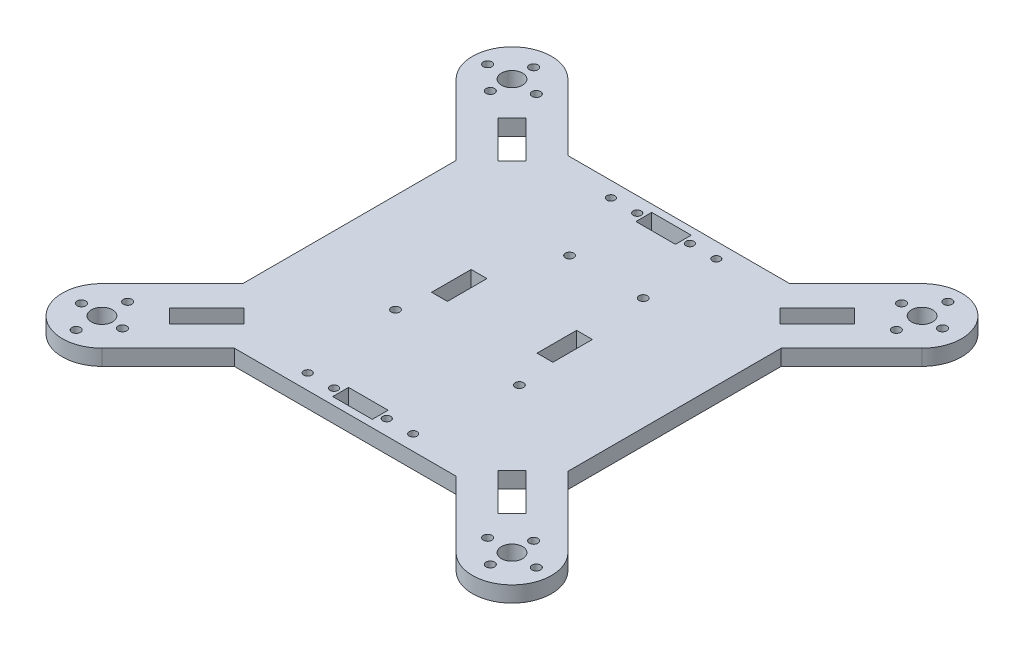
SolidWorks part; units mm, degrees
ref_plane "Front Plane" through (0, 0, 0) normal (0, 0, 1) x (1, 0, 0)
ref_plane "Top Plane" through (0, 0, 0) normal (0, 1, 0) x (1, 0, 0)
ref_plane "Right Plane" through (0, 0, 0) normal (1, 0, 0) x (0, 0, -1)
sketch "Sketch1" plane through (0, 0, 0) normal (0, 1, 0) x (1, 0, 0)
  line L0 (-67.1751, 88.3883) -> (88.3883, -67.1751)
  line L1 (-77.7817, 77.7817) -> (77.7817, 77.7817) construction
  line L2 (-77.7817, 77.7817) -> (-77.7817, -77.7817) construction
  line L3 (-77.7817, -77.7817) -> (77.7817, -77.7817) construction
  line L4 (77.7817, 77.7817) -> (77.7817, -77.7817) construction
  line L5 (-77.7817, 77.7817) -> (77.7817, -77.7817) construction
  line L6 (-77.7817, -77.7817) -> (77.7817, 77.7817) construction
  line L7 (67.1751, 88.3883) -> (-88.3883, -67.1751)
  line L8 (88.3883, 67.1751) -> (-67.1751, -88.3883)
  line L9 (-88.3883, 67.1751) -> (67.1751, -88.3883)
  line L10 (0, -1000) -> (0, 49000) construction
  line L11 (-1000, 0) -> (49000, 0) construction
  circle A0 centre (-77.7817, 77.7817) radius 15
  circle A1 centre (77.7817, 77.7817) radius 15
  circle A2 centre (-77.7817, -77.7817) radius 15
  circle A3 centre (77.7817, -77.7817) radius 15
  circle A4 centre (-77.7817, 77.7817) radius 4
  circle A5 centre (77.7817, 77.7817) radius 4
  circle A6 centre (77.7817, -77.7817) radius 4
  circle A7 centre (-77.7817, -77.7817) radius 4
  point P0 (0, 0)
  point P14 (10.6066, 10.6066)
  point P16 (10.6066, -10.6066)
  dimension "D4" = 8
  dimension "D1" = 220
  dimension "D2" = 30
  dimension "D3" = 30
extrude "Boss-Extrude1" add sketch "Sketch1" along normal blind 6 contours A0 A4 | A0 L9 L7 L0 | A2 A7 | L7 A2 L8 L9 | A3 L0 L8 L9 | L8 A1 L7 L0 | L7 L9 L8 L0 | A3 A6 | A1 A5 region at (-40.0766, 0, -40.0766) region at (-64.3155, 0, -83.3596) region at (40.0766, 0, -40.0766) region at (0, 0, 0) region at (40.0766, 0, 40.0766) region at (83.3596, 0, -91.248) region at (-40.0766, 0, 40.0766) region at (91.248, 0, 72.2039) region at (-72.2039, 0, 64.3155)
sketch "Sketch5" plane through (0, 6, 0) normal (0, 1, 0) x (1, 0, 0)
  line L0 (26.67, -35.3069) -> (-26.67, -35.3069)
  line L1 (26.67, -35.3069) -> (26.67, 30.7331)
  line L2 (21.59, 33.2731) -> (-11.176, 33.2731)
  line L3 (-26.67, -35.3069) -> (-26.67, 30.7331)
  line L4 (-26.67, 30.7331) -> (-13.716, 30.7331)
  line L5 (-13.716, 30.7331) -> (-11.176, 33.2731)
  line L6 (21.59, 33.2731) -> (24.13, 30.7331)
  line L7 (24.13, 30.7331) -> (26.67, 30.7331)
  line L8 (0, -1000) -> (0, 49000) construction
  line L10 (-1000, 0) -> (49000, 0) construction
  circle A0 centre (19.05, 30.7331) radius 1.5875
  circle A1 centre (-8.89, 30.7331) radius 1.5875
  circle A2 centre (24.13, -21.3369) radius 1.5875
  circle A3 centre (-24.13, -20.0669) radius 1.5875
  point P20 (0, -35.3069)
  line M10 (0, 21.2132) -> (-67.1751, 88.3883)
  line M12 (-88.3883, 67.1751) -> (-21.2132, 0)
  line M13 (-21.2132, 0) -> (-88.3883, -67.1751)
  line M15 (-67.1751, -88.3883) -> (0, -21.2132)
  line M16 (0, -21.2132) -> (67.1751, -88.3883)
  line M18 (88.3883, -67.1751) -> (21.2132, 0)
  line M19 (21.2132, 0) -> (88.3883, 67.1751)
  line M21 (67.1751, 88.3883) -> (0, 21.2132)
  dimension "D5" = 3.175
  dimension "D1" = 2.54
  dimension "D2" = 45
  dimension "D3" = 40.386
  dimension "D4" = 45
  dimension "D6" = 35.56
  dimension "D7" = 7.62
  dimension "D8" = 2.54
  dimension "D9" = 50.8
  dimension "D10" = 13.97
  dimension "D11" = 15.24
  dimension "D12" = 53.34
  dimension "D13" = 66.04
  dimension "D14" = 3.5921
  dimension "D15" = 2.54
  dimension "D16" = 2.54
  dimension "D17" = 2.54
  dimension "D18" = 32.766
  dimension "D19" = 66.04
  dimension "D20" = 12.954
extrude "Boss-Extrude2" add sketch "Sketch5" against normal blind 6 contours A1 M10 | A1 L5 L4 L3 L0 L1 L7 L6 L2 A3 A2 A0 M10 M12 M13 M15 M16 M18 M19 M21 | L3 M13 M12 | L1 M18 M19 | L0 M16 M15 | A1 L2 L5 M10 M21 region at (0.1063, 6, 1.0525) region at (0, 6, 30.609) region at (24.8511, 6, 0) region at (-24.8511, 6, 0) region at (0.3445, 6, -29.1791) region at (-8.5785, 6, -31.0446)
extrude "Cut-Extrude1" cut sketch "Sketch5<3>" against normal through all contours A1 | A0 | A2 | A3
sketch "Sketch5<3>" plane through (0, 6, 0) normal (0, 1, 0) x (1, 0, 0) same geometry as "Sketch5"
sketch "Sketch6" plane through (0, 6, 0) normal (0, 1, 0) x (1, 0, 0)
  line L0 (-1000, 0) -> (49000, 0) construction
  line L1 (0, -1000) -> (0, 49000) construction
  line L2 (0, 0) -> (-35355.3391, 35355.3391) construction
  line L3 (0, 0) -> (35355.3391, 35355.3391) construction
  line L4 (-77.5182, -68.2854) -> (-78.0453, -87.2781) construction
  line L5 (-69.7848, -78.0037) -> (-85.7787, -77.5598) construction
  circle A4 centre (-69.7848, -78.0037) radius 1.625
  circle A5 centre (-78.0453, -87.2781) radius 1.625
  circle A6 centre (-77.5182, -68.2854) radius 1.625
  circle A7 centre (-85.7787, -77.5598) radius 1.625
  circle A28 centre (-77.7817, -77.7817) radius 4 construction
  circle A29 centre (-77.7817, -77.7817) radius 4
  circle A30 centre (68.2854, -77.5182) radius 1.625
  circle A31 centre (87.2781, -78.0453) radius 1.625
  circle A32 centre (78.0037, -69.7848) radius 1.625
  circle A33 centre (77.5598, -85.7787) radius 1.625
  circle A38 centre (-87.2781, 78.0453) radius 1.625
  circle A39 centre (-77.5598, 85.7787) radius 1.625
  circle A40 centre (-78.0037, 69.7848) radius 1.625
  circle A41 centre (-68.2854, 77.5182) radius 1.625
  circle A42 centre (78.0453, 87.2781) radius 1.625
  circle A43 centre (77.5182, 68.2854) radius 1.625
  circle A44 centre (85.7787, 77.5598) radius 1.625
  circle A45 centre (69.7848, 78.0037) radius 1.625
  dimension "D1" = 18.9927
  dimension "D2" = 15.9938
  dimension "D3" = 9.7183
  dimension "D4" = 12.4197
  dimension "D5" = 12.4197
  dimension "D6" = 12.4197
extrude "Cut-Extrude2" cut sketch "Sketch6" against normal up to next (6 mm away)
sketch "Sketch7" plane through (0, 6, 0) normal (0, 1, 0) x (1, 0, 0)
  line L0 (88.3883, 67.1751) -> (26.67, 5.4568) construction
  line L1 (26.67, -5.4568) -> (26.67, 5.4568) construction
  line L2 (26.67, -5.4568) -> (88.3883, -67.1751) construction
  line L3 (-26.67, -5.4568) -> (-88.3883, -67.1751) construction
  line L4 (-88.3883, 67.1751) -> (-26.67, 5.4568) construction
  line L5 (-26.67, -5.4568) -> (-26.67, 5.4568) construction
  line L6 (88.3883, 67.1751) -> (26.67, 5.4568)
  line L7 (26.67, -5.4568) -> (26.67, 5.4568)
  line L8 (26.67, -5.4568) -> (88.3883, -67.1751)
  line L9 (-26.67, -5.4568) -> (-88.3883, -67.1751)
  line L10 (-88.3883, 67.1751) -> (-26.67, 5.4568)
  line L11 (-26.67, -5.4568) -> (-26.67, 5.4568)
  line L12 (-61.67, 40.4568) -> (-61.67, -40.4568)
  line L13 (0, -1000) -> (0, 49000) construction
  line L14 (61.67, 40.4568) -> (61.67, -40.4568)
  line L15 (-11.6179, 32.8311) -> (-11.176, 33.2731) construction
  line L16 (67.1751, 88.3883) -> (12.0599, 33.2731) construction
  line L17 (12.0599, 33.2731) -> (-11.176, 33.2731) construction
  line L18 (-67.1751, 88.3883) -> (-11.6179, 32.8311) construction
  line L19 (-11.6179, 32.8311) -> (-11.176, 33.2731)
  line L20 (67.1751, 88.3883) -> (12.0599, 33.2731)
  line L21 (12.0599, 33.2731) -> (-11.176, 33.2731)
  line L22 (-67.1751, 88.3883) -> (-11.6179, 32.8311)
  line L23 (14.0937, -35.3069) -> (67.1751, -88.3883) construction
  line L24 (14.0937, -35.3069) -> (-14.0937, -35.3069) construction
  line L25 (-14.0937, -35.3069) -> (-67.1751, -88.3883) construction
  line L26 (14.0937, -35.3069) -> (67.1751, -88.3883)
  line L27 (14.0937, -35.3069) -> (-14.0937, -35.3069)
  line L28 (-14.0937, -35.3069) -> (-67.1751, -88.3883)
  line L29 (-1000, 0) -> (49000, 0) construction
  line L30 (-42.0599, 63.2731) -> (42.0599, 63.2731)
  line L31 (-42.0599, -63.2731) -> (42.0599, -63.2731)
  line M25 (-14.0937, -35.3069) -> (14.0937, -35.3069)
  line M26 (14.0937, -35.3069) -> (67.1751, -88.3883)
  line M29 (26.67, -5.4568) -> (26.67, 5.4568)
  line M30 (26.67, 5.4568) -> (88.3883, 67.1751)
  line M33 (12.0599, 33.2731) -> (-11.176, 33.2731)
  line M34 (-11.176, 33.2731) -> (-11.6179, 32.8311)
  line M35 (-11.6179, 32.8311) -> (-67.1751, 88.3883)
  line M38 (-26.67, 5.4568) -> (-26.67, -5.4568)
  line M39 (-26.67, -5.4568) -> (-88.3883, -67.1751)
  dimension "D1" = 35
  dimension "D2" = 30
extrude "Boss-Extrude3" add sketch "Sketch7" against normal blind 6 contours L14 L8 M30 M29 | L10 L12 M39 M38 | L28 L31 M26 M25 | L30 L20 M35 M34 M33 region at (48.6168, 6, 0) region at (-48.6168, 6, 0) region at (-0.0014, 6, -51.0425) region at (0, 6, 51.6113)
sketch "Sketch8" plane through (0, 6, 0) normal (0, 1, 0) x (1, 0, 0)
  line L0 (0, -1000) -> (0, 49000) construction
  line L1 (-1000, 0) -> (49000, 0) construction
  line L2 (-20, 57.5) -> (20, 57.5) construction
  line L3 (-20, -57.5) -> (-20, 57.5) construction
  line L4 (-20, -57.5) -> (20, -57.5) construction
  line L5 (20, 57.5) -> (20, -57.5) construction
  line L6 (-7.5, -54.5) -> (7.5, -60.5) construction
  line L7 (-7.5, 60.5) -> (7.5, 60.5)
  line L8 (-7.5, 60.5) -> (-7.5, 54.5)
  line L9 (-7.5, 54.5) -> (7.5, 54.5)
  line L10 (7.5, 60.5) -> (7.5, 54.5)
  line L11 (-7.5, 60.5) -> (7.5, 54.5) construction
  line L12 (-7.5, 54.5) -> (7.5, 60.5) construction
  line L13 (-7.5, -60.5) -> (7.5, -54.5) construction
  line L14 (7.5, -60.5) -> (7.5, -54.5)
  line L15 (-7.5, -54.5) -> (7.5, -54.5)
  line L16 (-7.5, -60.5) -> (-7.5, -54.5)
  line L17 (-7.5, -60.5) -> (7.5, -60.5)
  line L18 (23, -7.5) -> (17, 7.5) construction
  line L19 (-23, 7.5) -> (-17, 7.5)
  line L20 (-23, 7.5) -> (-23, -7.5)
  line L21 (-23, -7.5) -> (-17, -7.5)
  line L22 (-17, 7.5) -> (-17, -7.5)
  line L23 (-23, 7.5) -> (-17, -7.5) construction
  line L24 (-23, -7.5) -> (-17, 7.5) construction
  line L25 (23, 7.5) -> (17, -7.5) construction
  line L26 (17, 7.5) -> (17, -7.5)
  line L27 (23, -7.5) -> (17, -7.5)
  line L28 (23, 7.5) -> (23, -7.5)
  line L29 (23, 7.5) -> (17, 7.5)
  circle A0 centre (-20, 57.5) radius 1.5
  circle A1 centre (20, 57.5) radius 1.5
  circle A2 centre (20, -57.5) radius 1.5
  circle A3 centre (-20, -57.5) radius 1.5
  circle A4 centre (-10, 57.5) radius 1.5
  circle A5 centre (10, 57.5) radius 1.5
  circle A6 centre (-10, -57.5) radius 1.5
  circle A7 centre (10, -57.5) radius 1.5
  point P15 (0, 57.5)
  point P32 (0, -57.5)
  point P33 (-20, 0)
  point P41 (20, 0)
  dimension "D3" = 3
  dimension "D4" = 3
  dimension "D5" = 3
  dimension "D6" = 3
  dimension "D8" = 3
  dimension "D1" = 40
  dimension "D2" = 115
  dimension "D7" = 10
  dimension "D9" = 6
  dimension "D10" = 15
  dimension "D11" = 6
  dimension "D12" = 15
extrude "Cut-Extrude7" cut sketch "Sketch8" along normal blind 6 and the other way through all
sketch "Sketch9" plane through (0, 6, 0) normal (0, 1, 0) x (1, 0, 0)
  line L0 (-1000, 0) -> (49000, 0) construction
  line L1 (0, -1000) -> (0, 49000) construction
  line L2 (0, 0) -> (-35355.3391, 35355.3391) construction
  line L3 (-67.6003, 62.297) -> (-62.297, 67.6003)
  line L4 (-67.6003, 62.297) -> (-53.4581, 48.1548)
  line L5 (-53.4581, 48.1548) -> (-48.1548, 53.4581)
  line L6 (-62.297, 67.6003) -> (-48.1548, 53.4581)
  line L7 (-67.6003, 62.297) -> (-48.1548, 53.4581) construction
  line L8 (-53.4581, 48.1548) -> (-62.297, 67.6003) construction
  line L9 (0, 0) -> (35355.3391, 35355.3391) construction
  line L10 (-88.3883, 67.1751) -> (-61.67, 40.4568) construction
  line L11 (53.4581, 48.1548) -> (62.297, 67.6003) construction
  line L12 (67.6003, 62.297) -> (48.1548, 53.4581) construction
  line L13 (62.297, 67.6003) -> (48.1548, 53.4581)
  line L14 (53.4581, 48.1548) -> (48.1548, 53.4581)
  line L15 (67.6003, 62.297) -> (53.4581, 48.1548)
  line L16 (67.6003, 62.297) -> (62.297, 67.6003)
  line L17 (67.6003, -62.297) -> (48.1548, -53.4581) construction
  line L18 (53.4581, -48.1548) -> (62.297, -67.6003) construction
  line L19 (-53.4581, -48.1548) -> (-62.297, -67.6003) construction
  line L20 (-67.6003, -62.297) -> (-48.1548, -53.4581) construction
  line L21 (67.6003, -62.297) -> (62.297, -67.6003)
  line L22 (67.6003, -62.297) -> (53.4581, -48.1548)
  line L23 (53.4581, -48.1548) -> (48.1548, -53.4581)
  line L24 (62.297, -67.6003) -> (48.1548, -53.4581)
  line L25 (-62.297, -67.6003) -> (-48.1548, -53.4581)
  line L26 (-53.4581, -48.1548) -> (-48.1548, -53.4581)
  line L27 (-67.6003, -62.297) -> (-53.4581, -48.1548)
  line L28 (-67.6003, -62.297) -> (-62.297, -67.6003)
  point P4 (-57.8775, 57.8775)
  point P20 (57.8775, 57.8775)
  point P29 (57.8775, -57.8775)
  point P30 (-57.8775, -57.8775)
  dimension "D1" = 7.5
  dimension "D2" = 20
extrude "Cut-Extrude9" cut sketch "Sketch9" against normal through all
equation "\"Frame_Size\" = 220"
equation "\"Arm_Width\" = 30"
equation "\"Motor_Mount_Hole_Diameter\" = 8"
equation "\"Motor_Shaft_Diameter\" = 3"
equation "\"D1@Sketch1\"=\"Frame_Size\""
equation "\"D2@Sketch1\"=\"Arm_Width\""
equation "\"D3@Sketch1\"=\"Arm_Width\""
equation "\"D4@Sketch1\"=\"Motor_Mount_Hole_Diameter\""
equation "\"Frame_Thickness\" = 6"
equation "\"D1@Boss-Extrude1\"=\"Frame_Thickness\""
equation "\"D1@Boss-Extrude2\"=\"Frame_Thickness\""
equation "\"D1@Boss-Extrude3\"=\"Frame_Thickness\""
equation "\"Screw_Nut_Diameter\" = 6.5"
equation "\"Screw_Diameter\" = 3"
equation "\"Screw_Shaft_Length\" = 10"
equation "\"Screw_Hole_Separation_C2C\" = 20"
equation "\"Solder_Board_Small_Screw_Hole_Separation\" = 37"
equation "\"Solder_Board_Small_Screw_Hole_Diameter\" = 3.3"
equation "\"Solder_Board_Small_Length\" = 45.72"
equation "\"Solder_Board_Small_Width\" = 33.02"
equation "\"Solder_Board_Small_Thickness\" = 1.6"
equation "\"ESC_Length\" = 35"
equation "\"ESC_Width\" = 17"
equation "\"ESC_Thickness\" = 5"
equation "\"Battery_Length\" = 105"
equation "\"Battery_Width\" = 33"
equation "\"Battery_Thickness\" = 24"
equation "\"Battery_Holder_Screw_Hole_Distance_Long\" = 115"
equation "\"Battery_Holder_Screw_Hole_Distance_Short\" = 40"
equation "\"D1@Sketch8\"=\"Battery_Holder_Screw_Hole_Distance_Short\""
equation "\"D2@Sketch8\"=\"Battery_Holder_Screw_Hole_Distance_Long\""
equation "\"D3@Sketch8\"=\"Screw_Diameter\""
equation "\"D4@Sketch8\"=\"Screw_Diameter\""
equation "\"D5@Sketch8\"=\"Screw_Diameter\""
equation "\"D6@Sketch8\"=\"Screw_Diameter\""
equation "\"D8@Sketch8\"=\"Screw_Diameter\""
equation "\"D7@Sketch8\"=\"Battery_Holder_Screw_Hole_Distance_Short\"/4"
equation "\"D9@Sketch8\"=\"Frame_Thickness\""
equation "\"Screw_Nut_Thickness\" = 2.5"
equation "\"Tooth_Width\" = 15"
equation "\"D10@Sketch8\"=\"Tooth_Width\""
equation "\"D11@Sketch8\"=\"Frame_Thickness\""
equation "\"D12@Sketch8\"=\"Tooth_Width\""
